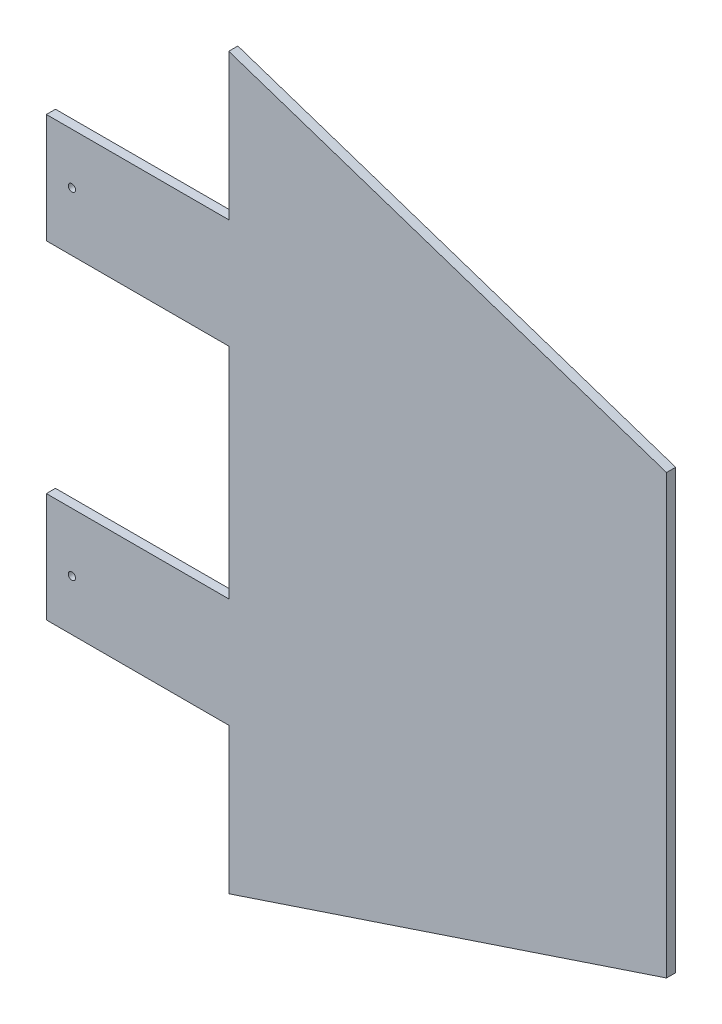
SolidWorks part; units mm, degrees
ref_plane "Front Plane" through (0, 0, 0) normal (0, 0, 1) x (1, 0, 0)
ref_plane "Top Plane" through (0, 0, 0) normal (0, 1, 0) x (1, 0, 0)
ref_plane "Right Plane" through (0, 0, 0) normal (1, 0, 0) x (0, 0, -1)
sketch "Sketch1" plane through (0, 0, 0) normal (0, 0, 1) x (1, 0, 0)
  line L0 (0, 374.2151) -> (0, -368.9959) construction
  line L1 (-577.763, 0) -> (528.7027, 0) construction
  line L3 (95.25, 127) -> (247.65, 76.2)
  line L4 (247.65, 76.2) -> (247.65, -76.2)
  line L5 (95.25, -127) -> (247.65, -76.2)
  line L6 (95.25, 76.2) -> (31.75, 76.2)
  line L7 (31.75, 76.2) -> (31.75, 38.1)
  line L8 (31.75, 38.1) -> (95.25, 38.1)
  line L13 (95.25, 127) -> (95.25, 76.2)
  line L14 (95.25, 38.1) -> (95.25, -38.1)
  line L15 (31.75, -38.1) -> (95.25, -38.1)
  line L16 (31.75, -76.2) -> (31.75, -38.1)
  line L17 (95.25, -76.2) -> (31.75, -76.2)
  line L18 (95.25, -127) -> (95.25, -76.2)
  point P10 (247.65, 0)
  point P11 (95.25, 0)
  point P17 (95.25, 0)
  dimension "D1" = 152.4
  dimension "D2" = 76.2
  dimension "D3" = 127
  dimension "D5" = 38.1
  dimension "D6" = 63.5
extrude "Boss-Extrude1" add sketch "Sketch1" along normal blind 1.5875 and the other way blind 1.5875
sketch "Sketch2" plane through (0, 0, 1.5875) normal (0, 0, 1) x (1, 0, 0)
  line L0 (31.75, 76.2) -> (31.75, 38.1) construction
  line L1 (9.4003, 0) -> (247.65, 0) construction
  line L2 (247.65, -76.2) -> (247.65, 76.2) construction
  circle A0 centre (40.64, 58.5126) radius 1.2662
  circle A1 centre (40.64, -58.5126) radius 1.2662
  dimension "D2" = 2.5324
  dimension "D1" = 8.89
extrude "Cut-Extrude1" cut sketch "Sketch2" against normal through all contours A0 | A1
